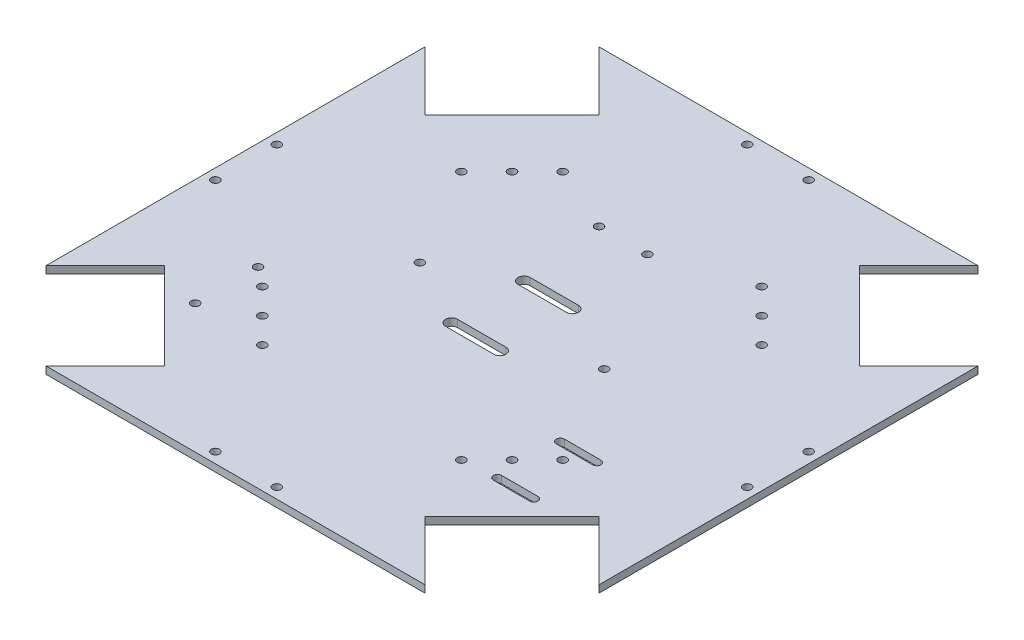
SolidWorks part; units mm, degrees
ref_plane "Front Plane" through (0, 0, 0) normal (0, 0, 1) x (1, 0, 0)
ref_plane "Top Plane" through (0, 0, 0) normal (0, 1, 0) x (1, 0, 0)
ref_plane "Right Plane" through (0, 0, 0) normal (1, 0, 0) x (0, 0, -1)
sketch "Sketch1" plane through (0, 0, 0) normal (0, 1, 0) x (1, 0, 0)
  line L1 (-114.3, 114.3) -> (114.3, 114.3)
  line L2 (-114.3, 114.3) -> (-114.3, -114.3)
  line L3 (-114.3, -114.3) -> (114.3, -114.3)
  line L4 (114.3, 114.3) -> (114.3, -114.3)
  line L5 (-114.3, 114.3) -> (114.3, -114.3) construction
  line L6 (-114.3, -114.3) -> (114.3, 114.3) construction
  point P0 (0, 0)
  dimension "D1" = 228.6
  dimension "D2" = 228.6
extrude "plate" add sketch "Sketch1" along normal blind 3
sketch "Sketch8" plane through (0, 3, 0) normal (0, 1, 0) x (1, 0, 0)
  line L0 (-114.3, 114.3) -> (114.3, -114.3) construction
  line L1 (114.3, 114.3) -> (-114.3, -114.3) construction
  line L2 (-62.6812, 165.9188) -> (165.9188, -62.6812) construction
  line L3 (0, 0) -> (51.6188, 51.6188) construction
  circle A0 centre (51.6188, 51.6188) radius 1.7
  circle A1 centre (62.084, 41.1536) radius 1.7
  circle A2 centre (41.1536, 62.084) radius 1.7
  circle A3 centre (51.6188, -51.6188) radius 1.7
  circle A4 centre (62.084, -41.1536) radius 1.7
  circle A5 centre (41.1536, -62.084) radius 1.7
  circle A6 centre (-51.6188, -51.6188) radius 1.7
  circle A7 centre (-41.1536, -62.084) radius 1.7
  circle A8 centre (-62.084, -41.1536) radius 1.7
  circle A9 centre (-51.6188, 51.6188) radius 1.7
  circle A10 centre (-62.084, 41.1536) radius 1.7
  circle A11 centre (-41.1536, 62.084) radius 1.7
  dimension "D2" = 3.4
  dimension "D3" = 3.4
  dimension "D4" = 3.4
  dimension "D5" = 14.8
  dimension "D6" = 14.8
  dimension "D8" = 73
  dimension "D9" = 73
  dimension "D1" = 73
  dimension "D7" = 4
extrude "motor-mount-holes" cut sketch "Sketch8" against normal blind 3
sketch "Sketch9" plane through (0, 3, 0) normal (0, 1, 0) x (1, 0, 0)
  line L0 (0, -114.3) -> (0, 114.3) construction
  line L2 (114.3, -114.3) -> (114.3, 114.3) construction
  line L3 (-114.3, 0) -> (114.3, 0) construction
  line L4 (114.3, 114.3) -> (-114.3, 114.3) construction
  line L5 (-114.3, -114.3) -> (114.3, -114.3) construction
  line L6 (-114.3, 114.3) -> (-114.3, -114.3) construction
  circle A0 centre (-38.13, 0) radius 1.7
  circle A1 centre (38.13, 0) radius 1.7
  dimension "D3" = 3.4
  dimension "D4" = 3.4
  dimension "D1" = 76.26
  dimension "D2" = 38.13
extrude "connector-board-holes" cut sketch "Sketch9" against normal blind 3
sketch "Sketch11" plane through (0, 3, 0) normal (0, 1, 0) x (1, 0, 0)
  line L0 (-114.3, 0) -> (114.3, 0) construction
  line L1 (-114.3, 50) -> (114.3, 50) construction
  line L2 (0, -114.3) -> (0, 114.3) construction
  line L3 (27.5, -114.3) -> (27.5, 114.3) construction
  line L4 (-27.5, -114.3) -> (-27.5, 114.3) construction
  line L5 (-123.5172, 0) -> (114.3, 0) construction
  line L6 (-114.3, 114.3) -> (-114.3, -114.3) construction
  line L7 (114.3, -114.3) -> (114.3, 114.3) construction
  line L8 (0, -94.2235) -> (0, 114.3) construction
  line L9 (114.3, 114.3) -> (-114.3, 114.3) construction
  line L10 (-114.3, -114.3) -> (114.3, -114.3) construction
  line L11 (-123.5172, 50) -> (114.3, 50) construction
  line L12 (-27.5, -94.2235) -> (-27.5, 114.3) construction
  line L13 (27.5, -94.2235) -> (27.5, 114.3) construction
  circle A0 centre (-14, 50) radius 1.7
  circle A1 centre (6, 50) radius 1.7
  dimension "D4" = 3.4
  dimension "D5" = 3.4
  dimension "D6" = 13.5
  dimension "D7" = 20
  dimension "D1" = 50
  dimension "D2" = 27.5
  dimension "D3" = 27.5
extrude "motor-controller-holder-arduino-holes" cut sketch "Sketch11" against normal up to next
sketch "Sketch12" plane through (0, 3, 0) normal (0, 1, 0) x (1, 0, 0)
  line L0 (114.3, 0) -> (-114.3, 0) construction
  line L1 (114.3, -114.3) -> (114.3, 114.3) construction
  line L2 (-114.3, 114.3) -> (-114.3, -114.3) construction
  line L3 (-10, 15) -> (10, 15) construction
  line L4 (-10, 17.5) -> (10, 17.5)
  line L5 (-10, 12.5) -> (10, 12.5)
  line L6 (-10, -15) -> (10, -15) construction
  line L7 (-10, -12.5) -> (10, -12.5)
  line L8 (-10, -17.5) -> (10, -17.5)
  line L9 (0, 114.3) -> (0, -114.3) construction
  line L10 (114.3, 114.3) -> (-114.3, 114.3) construction
  line L11 (-114.3, -114.3) -> (114.3, -114.3) construction
  arc A0 (-10, 17.5) -> (-10, 12.5) centre (-10, 15) ccw
  arc A1 (10, 12.5) -> (10, 17.5) centre (10, 15) ccw
  arc A2 (-10, -12.5) -> (-10, -17.5) centre (-10, -15) ccw
  arc A3 (10, -17.5) -> (10, -12.5) centre (10, -15) ccw
  point P8 (0, 15)
  point P13 (0, -15)
  dimension "D5" = 2.5
  dimension "D6" = 2.5
  dimension "D1" = 15
  dimension "D2" = 15
  dimension "D3" = 20
  dimension "D4" = 20
extrude "cable-slots" cut sketch "Sketch12" against normal up to next
sketch "Sketch13" plane through (0, 3, 0) normal (0, 1, 0) x (1, 0, 0)
  line L0 (0, -114.3) -> (0, 114.3) construction
  line L1 (-114.3, -114.3) -> (114.3, -114.3) construction
  line L2 (114.3, 114.3) -> (-114.3, 114.3) construction
  line L3 (-114.3, 109.9439) -> (114.3, 109.9439) construction
  line L4 (-114.3, 114.3) -> (-114.3, -114.3) construction
  line L5 (114.3, -114.3) -> (114.3, 114.3) construction
  line L6 (0, 0) -> (12.7, 109.9439) construction
  circle A0 centre (-12.7, 109.9439) radius 1.7
  circle A1 centre (12.7, 109.9439) radius 1.7
  circle A2 centre (109.9439, -12.7) radius 1.7
  circle A3 centre (109.9439, 12.7) radius 1.7
  circle A4 centre (-12.7, -109.9439) radius 1.7
  circle A5 centre (12.7, -109.9439) radius 1.7
  circle A6 centre (-109.9439, 12.7) radius 1.7
  circle A7 centre (-109.9439, -12.7) radius 1.7
  dimension "D2" = 3.4
  dimension "D3" = 3.4
  dimension "D1" = 4.3561
  dimension "D4" = 12.7
  dimension "D5" = 12.7
  dimension "D7" = 110.675
  dimension "D8" = 6.589
  dimension "D6" = 4
extrude "wall-bracket-holes" cut sketch "Sketch13" against normal up to next
sketch "Sketch14" plane through (0, 3, 0) normal (0, 1, 0) x (1, 0, 0)
  line L0 (-114.3, 0) -> (114.3, 0) construction
  line L1 (-114.3, 114.3) -> (-114.3, -114.3) construction
  line L2 (114.3, -114.3) -> (114.3, 114.3) construction
  line L3 (-114.3, -47) -> (114.3, -47) construction
  line L4 (0, 114.3) -> (0, -114.3) construction
  line L5 (114.3, 114.3) -> (-114.3, 114.3) construction
  line L6 (-114.3, -114.3) -> (114.3, -114.3) construction
  line L7 (55, -35) -> (70, -35) construction
  line L8 (55, -33.3) -> (70, -33.3)
  line L9 (55, -36.7) -> (70, -36.7)
  line L10 (55, -61) -> (70, -61) construction
  line L11 (55, -59.3) -> (70, -59.3)
  line L12 (55, -62.7) -> (70, -62.7)
  circle A0 centre (-70, -35) radius 1.7
  circle A1 centre (-70, -61) radius 1.7
  arc A2 (55, -33.3) -> (55, -36.7) centre (55, -35) ccw
  arc A3 (70, -36.7) -> (70, -33.3) centre (70, -35) ccw
  arc A4 (55, -59.3) -> (55, -62.7) centre (55, -61) ccw
  arc A5 (70, -62.7) -> (70, -59.3) centre (70, -61) ccw
  point P19 (62.5, -35)
  point P26 (62.5, -61)
  point P33 (0, 0)
  point P34 (0, 0)
  point P35 (0, 0)
  point P36 (0, 0)
  dimension "D5" = 3.4
  dimension "D6" = 3.4
  dimension "D9" = 1.7
  dimension "D10" = 1.7
  dimension "D2" = 70
  dimension "D3" = 12
  dimension "D4" = 14
  dimension "D7" = 55
  dimension "D8" = 15
  dimension "D1" = 47
extrude "battery-holder-holes" cut sketch "Sketch14" against normal up to next
sketch "Sketch2" plane through (0, 3, 0) normal (0, 1, 0) x (1, 0, 0)
  line L0 (-114.3, -114.3) -> (114.3, 114.3) construction
  line L1 (114.3, -114.3) -> (-114.3, 114.3) construction
  line L2 (-96.3395, -132.2605) -> (132.2605, 96.3395) construction
  line L3 (-132.2605, -96.3395) -> (96.3395, 132.2605) construction
  line L4 (186.142, -42.458) -> (-42.458, 186.142) construction
  line L5 (114.3, 114.3) -> (78.379, 114.3)
  line L6 (114.3, 114.3) -> (-114.3, 114.3) construction
  line L7 (78.379, 114.3) -> (53.8815, 89.8026)
  line L8 (53.8815, 89.8026) -> (89.8026, 53.8815)
  line L9 (89.8026, 53.8815) -> (114.3, 78.379)
  line L10 (114.3, 78.379) -> (114.3, 114.3)
  line L11 (78.379, -114.3) -> (114.3, -114.3)
  line L12 (114.3, -114.3) -> (114.3, -78.379)
  line L13 (114.3, -78.379) -> (89.8026, -53.8815)
  line L14 (89.8026, -53.8815) -> (53.8815, -89.8026)
  line L15 (53.8815, -89.8026) -> (78.379, -114.3)
  line L16 (-114.3, -78.379) -> (-114.3, -114.3)
  line L17 (-114.3, -114.3) -> (-78.379, -114.3)
  line L18 (-78.379, -114.3) -> (-53.8815, -89.8026)
  line L19 (-53.8815, -89.8026) -> (-89.8026, -53.8815)
  line L20 (-89.8026, -53.8815) -> (-114.3, -78.379)
  line L21 (-78.379, 114.3) -> (-114.3, 114.3)
  line L22 (-114.3, 114.3) -> (-114.3, 78.379)
  line L23 (-114.3, 78.379) -> (-89.8026, 53.8815)
  line L24 (-89.8026, 53.8815) -> (-53.8815, 89.8026)
  line L25 (-53.8815, 89.8026) -> (-78.379, 114.3)
  line L26 (0, 0) -> (89.8026, 53.8815) construction
  line L27 (0, 0) -> (53.8815, -89.8026) construction
  dimension "D5" = 90
  dimension "D6" = 14.036
  dimension "D7" = 104.7269
  dimension "D1" = 25.4
  dimension "D2" = 25.4
  dimension "D3" = 101.6
  dimension "D4" = 4
extrude "wheel-slots" cut sketch "Sketch2" against normal blind 3
sketch "Sketch10" plane through (0, 3, 0) normal (0, 1, 0) x (1, 0, 0)
  line L0 (0, 114.3) -> (0, -114.3) construction
  line L1 (78.379, 114.3) -> (-78.379, 114.3) construction
  line L2 (-78.379, -114.3) -> (78.379, -114.3) construction
  line L3 (-114.3, 0) -> (114.3, 0) construction
  line L4 (-114.3, 78.379) -> (-114.3, -78.379) construction
  line L5 (114.3, -78.379) -> (114.3, 78.379) construction
  line L6 (0, 0) -> (0, 62.08) construction
  circle A1 centre (0, 62.08) radius 1.7
  circle A2 centre (62.08, 0) radius 1.7
  circle A3 centre (0, -62.08) radius 1.7
  circle A4 centre (-62.08, 0) radius 1.7
  dimension "D1" = 3.4
  dimension "D2" = 62.08
  dimension "D4" = 62.08
  dimension "D5" = 62.08
  dimension "D3" = 4
extrude "level2-standoff-holes" [suppressed] cut sketch "Sketch10" against normal blind 3
